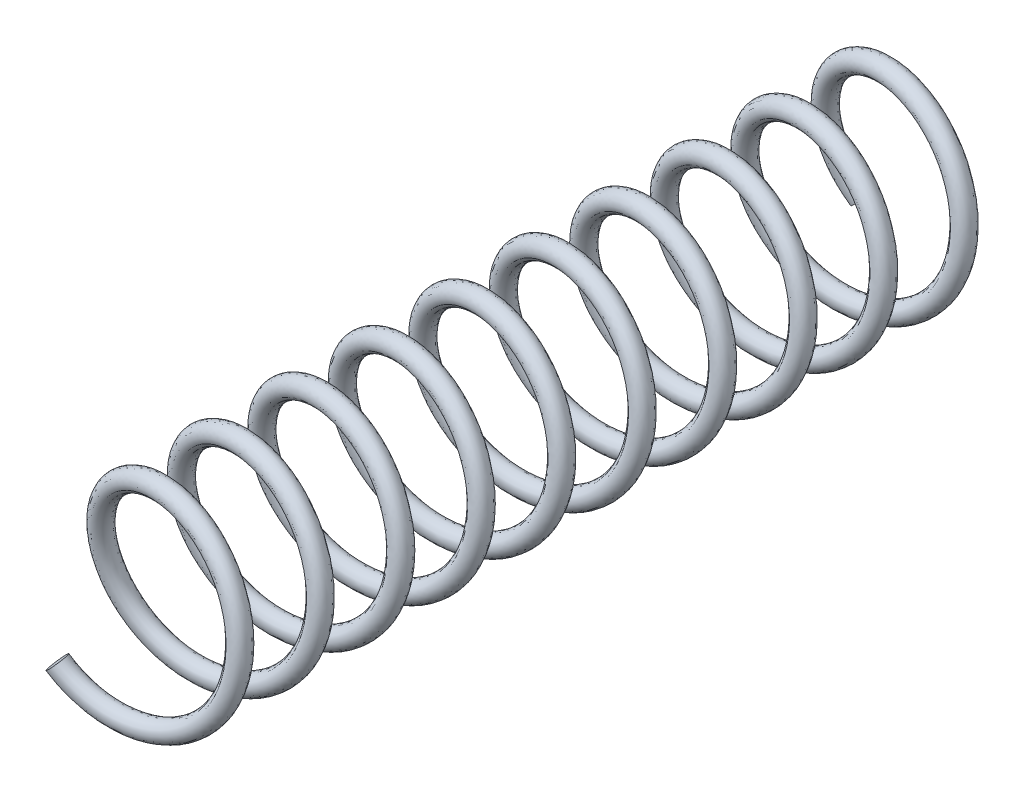
SolidWorks part; units mm, degrees
note: '?' marks a value the reader was unsure of.
ref_plane "Front Plane" through (0, 0, 0) normal (1, 0, 0) x (0, 1, 0)
ref_plane "Top Plane" through (0, 0, 0) normal (0, 0, 1) x (0, 1, 0)
ref_plane "Right Plane" through (0, 0, 0) normal (0, 1, 0) x (-1, 0, 0)
sketch "Sketch1" plane through (0, 0, 0) normal (0, 0, 1) x (0, 1, 0)
  circle A0 centre (0, 0) radius 11
  dimension "D1" = 22
curve "Helix/Spiral1" pitch 10 height 100 radius 11 left hand yes centre (0, 0, 0) axis (0, 0, 1) start towards (1, 0, 0)
sweep "Sweep2" add path "Helix/Spiral1" circular profile diameter 2.5 parameters "D3"=2.5
ref_axis "Axis1" through (0, 0, 107.7217) along (0, 0, -1)?
